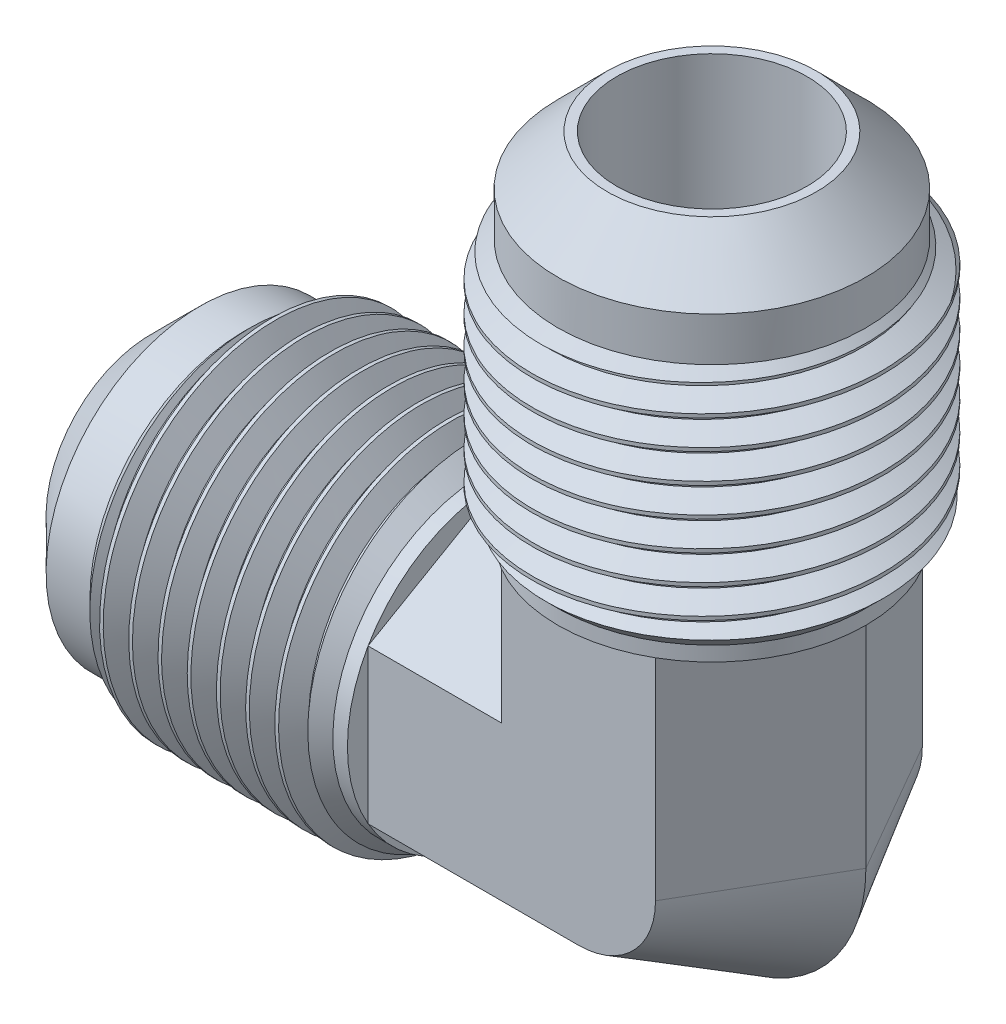
SolidWorks part; units mm, degrees
note: '?' marks a value the reader was unsure of.
material "Brass"
ref_plane "Front" through (0, 0, 0) normal (0, 0, 1) x (1, 0, 0)
ref_plane "Top" through (0, 0, 0) normal (0, 1, 0) x (1, 0, 0)
ref_plane "Right" through (0, 0, 0) normal (1, 0, 0) x (0, 0, -1)
sketch "Sketch1" plane through (0, 0, 0) normal (0, 0, 1) x (1, 0, 0)
  line L0 (0, 0) -> (19.05, 0)
  line L1 (19.05, 0) -> (19.05, 9.525)
  line L2 (19.05, 9.525) -> (0, 9.525)
  line L3 (0, 9.525) -> (0, 0)
  line L4 (0, 0) -> (66.207, 0) construction
  dimension "OD" = 19.05
  dimension "Thread Length" = 19.05
revolve "Revolve1" add sketch "Sketch1" angle 360 about L4
sketch "Sketch12" plane through (0, 0, 0) normal (-1, 0, 0) x (0, 0, 1)
  circle A1 centre (0, 0) radius 9.525
  circle A2 centre (0, 0) radius 9.525
  dimension "D1" = 0
curve "Helix/Spiral1" pitch 1.5875 height 20.6375 turns 13 parameters "Pitch"=1.5875
sketch "Sketch13" plane through (0, 0, 0) normal (0, 0, 1) x (1, 0, 0)
  line L0 (-1.3891, 9.525) -> (0, 9.525)
  line L1 (0, 9.525) -> (-0.5953, 8.4939)
  line L2 (-0.5953, 8.4939) -> (-0.7937, 8.4939)
  line L3 (-0.7937, 8.4939) -> (-1.3891, 9.525)
  line L4 (-0.6945, 8.4939) -> (-0.6945, 9.525) construction
  line L5 (-1.0914, 9.0094) -> (-0.2977, 9.0094) construction
  dimension "D1" = 60
  dimension "D2" = 0.1984
  dimension "D3" = 0.7937
sweep "Cut-Sweep2" cut profiles "Sketch13" path "Helix/Spiral1"
sketch "Sketch3" plane through (0, 0, 0) normal (0, 0, 1) x (1, 0, 0)
  line L0 (2.6811, 8.3669) -> (0, 5.6858)
  line L1 (2.6811, 8.3669) -> (5.0623, 8.3669)
  line L2 (5.0623, 8.3669) -> (6.2205, 9.525)
  line L3 (6.2205, 9.525) -> (0, 9.525)
  line L4 (0, 9.525) -> (0, 5.6858)
  line L5 (19.05, -6.0061) -> (19.05, 9.525) construction
  line L8 (0, 0) -> (19.05, 0) construction
  line L9 (0, 0) -> (66.207, 0) construction
  line L10 (-1.3891, 9.525) -> (0, 9.525) construction
  line L11 (19.05, 9.525) -> (19.05, 8.3669)
  line L12 (19.05, 8.3669) -> (18.2562, 8.3669)
  line L13 (18.2562, 8.3669) -> (17.0981, 9.525)
  line L14 (17.0981, 9.525) -> (19.05, 9.525)
  line L16 (0, 5.6858) -> (0, -5.6858) construction
  dimension "D4" = 0.127
  dimension "D2" = 45
  dimension "D3" = 2.3813
  dimension "D5" = 45
  dimension "D6" = 0.7937
  dimension "D1" = 11.3716
  dimension "D7" = 45
revolve "Cut-Revolve2" cut sketch "Sketch3" angle 360 about L8
sketch "Sketch11" plane through (0, 0, 0) normal (-1, 0, 0) x (0, 0, 1)
  circle A0 centre (0, 0) radius 5.1689
extrude "Cut-Extrude1" cut sketch "Sketch11" against normal through all
sketch "Sketch5" plane through (0, 0, 0) normal (0, 0, 1) x (1, 0, 0)
  line L0 (0, 0) -> (30.48, 0) construction
  line L1 (30.48, 0) -> (30.48, 30.48) construction
  dimension "M" = 30.48
ref_axis "Axis2" through (30.48, 0, 0) along (0, 0, 1)?
pattern_circular "CirPattern1" count 2 every 90 about axis through (30.48, 0, 0) along (0, 0, 1)
ref_plane "Plane1" through (19.05, 0, 0) normal (1, 0, 0) x (0, 0, -1)
sketch "Sketch6" plane through (0, 0, 0) normal (0, 0, 1) x (1, 0, 0)
  line L0 (19.05, 0) -> (17.3097, 0)
  line L1 (30.48, 13.1703) -> (30.48, 11.43)
  line L3 (30.48, 0) -> (21.9268, 8.5532) construction
  line L5 (0, 0) -> (30.48, 0) construction
  line L7 (19.05, -9.2036) -> (19.05, 9.2036) construction
  arc A0 (30.48, 13.1703) -> (17.3097, 0) centre (17.3097, 13.1703) cw
  dimension "D1" = 13.1703
sketch "Sketch7" plane through (19.05, 0, 0) normal (1, 0, 0) x (0, 0, -1)
  line L1 (7.2459, -4.1834) -> (7.2459, 4.1834)
  line L2 (7.2459, 4.1834) -> (0, 8.3669)
  line L3 (0, 8.3669) -> (-7.2459, 4.1834)
  line L4 (-7.2459, 4.1834) -> (-7.2459, -4.1834)
  line L5 (-7.2459, -4.1834) -> (0, -8.3669)
  line L6 (0, -8.3669) -> (7.2459, -4.1834)
  circle A0 centre (0, 0) radius 8.3669 construction
  circle A1 centre (0, 0) radius 5.1689 construction
  circle A2 centre (0, 0) radius 7.2459 construction
  circle A3 centre (0, 0) radius 5.1689
extrude "Boss-Extrude1" add sketch "Sketch7" along normal up to vertex (11.43 mm away) up to point (30.48, 0, 0)
sketch "Sketch14" plane through (0, 11.43, 0) normal (0, -1, 0) x (1, 0, 0)
  line L0 (30.48, 7.2459) -> (19.05, 7.2459) construction
  line L1 (26.2966, 7.2459) -> (22.1131, 0)
  line L2 (22.1131, 0) -> (26.2966, -7.2459)
  line L3 (26.2966, -7.2459) -> (34.6634, -7.2459)
  line L4 (34.6634, -7.2459) -> (38.8469, 0)
  line L5 (38.8469, 0) -> (34.6634, 7.2459)
  line L6 (34.6634, 7.2459) -> (26.2966, 7.2459)
  circle A0 centre (30.48, 0) radius 7.2459 construction
  circle A1 centre (30.48, 0) radius 5.1689 construction
  circle A2 centre (30.48, 0) radius 5.1689
extrude "Boss-Extrude2" add sketch "Sketch14" along normal up to vertex (11.43 mm away) up to point (30.48, 0, 0)
sketch "Sketch15" plane through (0, 0, 0) normal (0, -1, 0) x (1, 0, 0)
  line L6 (30.48, -5.1689) -> (30.48, -7.2459)
  line L7 (30.48, -7.2459) -> (34.6634, -7.2459)
  line L8 (34.6634, -7.2459) -> (38.8469, 0)
  line L9 (38.8469, 0) -> (34.6634, 7.2459)
  line L10 (34.6634, 7.2459) -> (30.48, 7.2459)
  line L11 (30.48, -5.1689) -> (30.48, -7.2459)
  line L12 (30.48, 7.2459) -> (30.48, 5.1689)
  line L13 (30.48, -7.2459) -> (34.6634, -7.2459)
  line L14 (34.6634, -7.2459) -> (38.8469, 0)
  line L15 (38.8469, 0) -> (34.6634, 7.2459)
  line L16 (34.6634, 7.2459) -> (30.48, 7.2459)
  line L17 (30.48, 7.2459) -> (30.48, 5.1689)
  arc A1 (30.48, -5.1689) -> (30.48, 5.1689) centre (30.48, 0) ccw
  arc A2 (30.48, -5.1689) -> (30.48, 5.1689) centre (30.48, 0) ccw
  dimension "D1" = 0
revolve "Revolve2" add sketch "Sketch15" angle 90 about L17
sketch "Sketch16" plane through (0, 30.48, 0) normal (0, 1, 0) x (1, 0, 0)
  circle A0 centre (30.48, 0) radius 5.1689 construction
  circle A1 centre (30.48, 0) radius 5.1689
extrude "Cut-Extrude2" cut sketch "Sketch16" against normal up to vertex (30.48 mm away) up to point (30.48, 0, 0)
sketch "Sketch17" plane through (0, 0, 0) normal (-1, 0, 0) x (0, 0, 1)
  circle A0 centre (0, 0) radius 5.1689 construction
  circle A1 centre (0, 0) radius 5.1689
extrude "Cut-Extrude3" cut sketch "Sketch17" against normal up to vertex (30.48 mm away) up to point (30.48, 0, 0)
equation "\"D2@Sketch13\" = \"Pitch@Helix/Spiral1\"*.125"
equation "\"D3@Sketch13\" = \"Pitch@Helix/Spiral1\"*.50"
equation "\"D3@Helix/Spiral1\" = \"Thread Length@Sketch1\"+\"Pitch@Helix/Spiral1\""
equation "\"D3@Sketch3\" = \"Pitch@Helix/Spiral1\"*1.50"
equation "\"D6@Sketch3\" = \"Pitch@Helix/Spiral1\"*.50"
equation "\"D1@Sketch3\" = \"ID@Sketch11\"*1.1"
